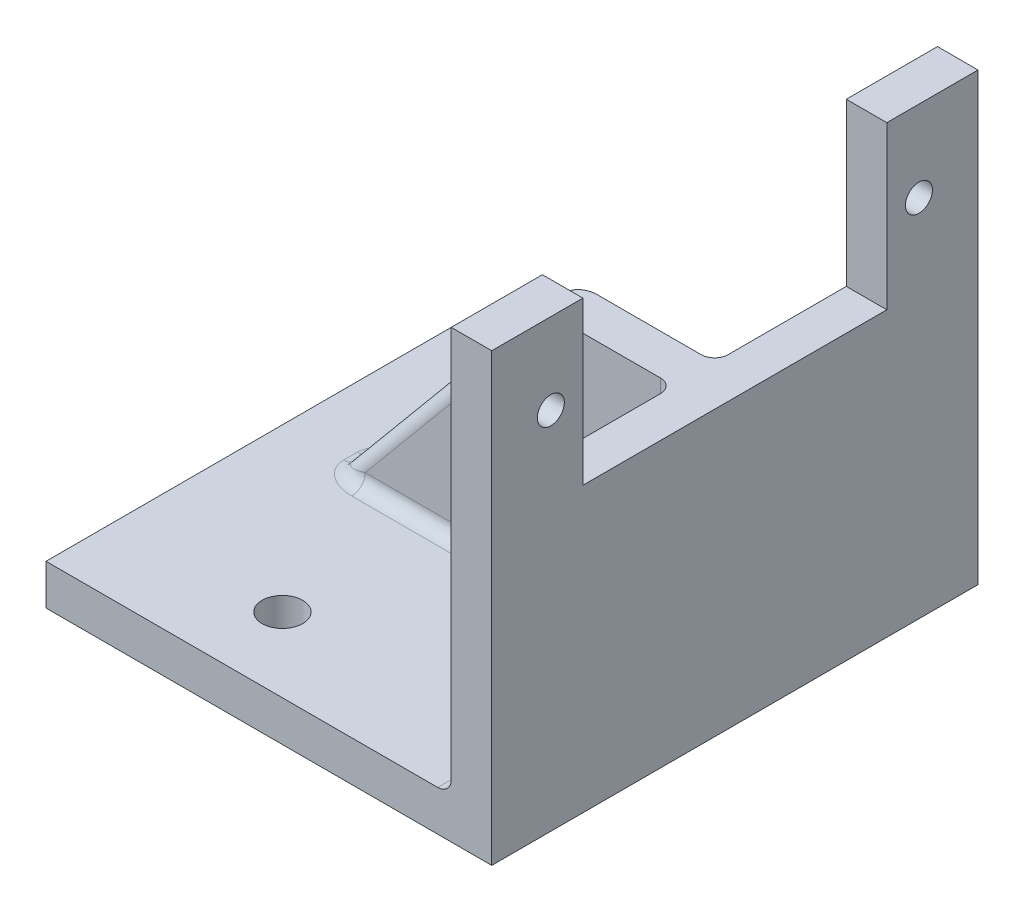
SolidWorks part; units mm, degrees
ref_plane "Front Plane" through (0, 0, 0) normal (0, 0, 1) x (1, 0, 0)
ref_plane "Top Plane" through (0, 0, 0) normal (0, 1, 0) x (1, 0, 0)
ref_plane "Right Plane" through (0, 0, 0) normal (1, 0, 0) x (0, 0, -1)
sketch "Sketch1" plane through (0, 0, 0) normal (0, 0, 1) x (1, 0, 0)
  line L0 (0, 0) -> (-30, 0)
  line L1 (0, 0) -> (0, 30)
  dimension "D1" = 30
  dimension "D2" = 30
extrude "Extrude-Thin1" add sketch "Sketch1" along normal mid plane 36 thin thin type one direction wall 3
sketch "Sketch2" plane through (0, 0, 0) normal (-1, 0, 0) x (0, 0, 1)
  line L0 (18, 30) -> (-18, 30) construction
  line L3 (-11.25, 18) -> (11.25, 18)
  line L5 (-11.25, 18) -> (-11.25, 30)
  line L6 (-11.25, 30) -> (11.25, 30)
  line L7 (11.25, 30) -> (11.25, 18)
  point P0 (0, 30)
  dimension "D1" = 12
  dimension "D2" = 22.5
  dimension "D3" = 11.25
extrude "Cut-Extrude1" cut sketch "Sketch2" against normal blind 10
sketch "Sketch3" plane through (0, 0, 0) normal (-1, 0, 0) x (0, 0, 1)
  line L0 (0, 0) -> (0, 32.9234) construction
  line L1 (0, 32.9234) -> (0, 39.1906) construction
  line L6 (14.625, 30) -> (-18.6665, 30) construction
  line L7 (18, 30) -> (11.25, 30) construction
  line L8 (1.7231, 18) -> (-20.4614, 18) construction
  line L9 (-11.25, 18) -> (11.25, 18) construction
  circle A0 centre (-13.625, 24) radius 1
  circle A1 centre (13.625, 24) radius 1
  dimension "D1" = 6
  dimension "D2" = 2
  dimension "D3" = 27.25
extrude "Cut-Extrude2" cut sketch "Sketch3" against normal blind 10
sketch "Sketch4" plane through (0, 0, 0) normal (0, 0, 1) x (1, 0, 0)
  line L0 (0, 0) -> (0, 18)
  line L1 (0, 0) -> (0, 30) construction
  line L2 (0, 18) -> (-10, 18)
  line L3 (-10, 18) -> (-25, 0)
  line L4 (-30, 0) -> (0, 0) construction
  line L5 (-25, 0) -> (0, 0)
  dimension "D1" = 18
  dimension "D2" = 25
  dimension "D3" = 10
extrude "Boss-Extrude1" add sketch "Sketch4" along normal mid plane 3
sketch "Sketch5" plane through (0, 0, 0) normal (0, 1, 0) x (1, 0, 0)
  line L0 (0, 0) -> (-33.506, 0) construction
  line L2 (-30, -18) -> (-30, 18) construction
  circle A0 centre (-18, 12.5) radius 1.5
  circle A1 centre (-18, -12.5) radius 1.5
  dimension "D1" = 25
  dimension "D2" = 3
  dimension "D3" = 12
extrude "Cut-Extrude3" cut sketch "Sketch5" against normal blind 3
fillet "Fillet1" radius 1 2 edges at (-17.5, 9, 1.5) (-17.5, 9, -1.5)
fillet "Fillet2" radius 1 5 edges at (-11.8491, 0, -1.5) (-24.6187, 0, -1.2071) (-25, 0, 0) (-24.6187, 0, 1.2071) (-11.8491, 0, 1.5)
fillet "Fillet3" radius 1 6 edges at (0, 0.2929, -1.7929) (0, 9.5, -1.5) (0, 0, -10.25) (0, 0.2929, 1.7929) (0, 0, 10.25) (0, 9.5, 1.5)
